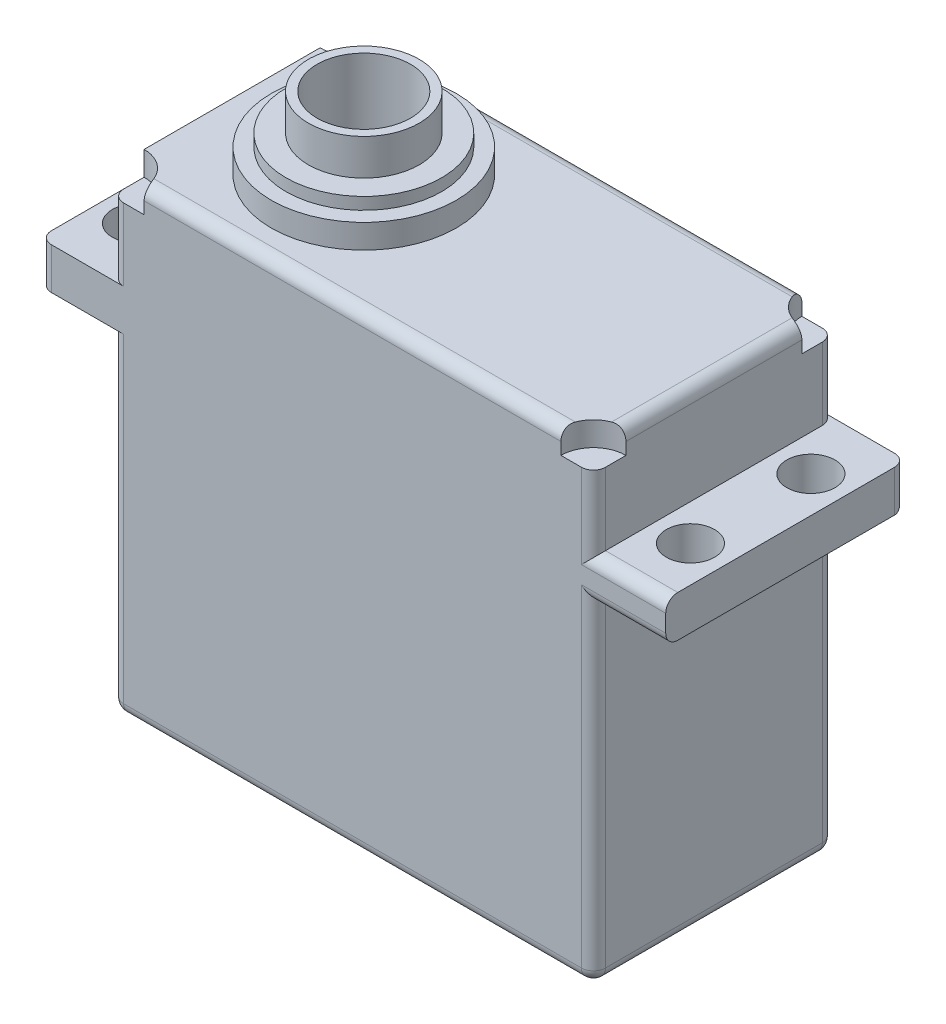
SolidWorks part; units mm, degrees
ref_plane "前视基准面" through (0, 0, 0) normal (0, 0, 1) x (1, 0, 0)
ref_plane "上视基准面" through (0, 0, 0) normal (0, 1, 0) x (1, 0, 0)
ref_plane "右视基准面" through (0, 0, 0) normal (1, 0, 0) x (0, 0, -1)
sketch "草图1" plane through (0, 0, 0) normal (0, 0, 1) x (1, 0, 0)
  line L0 (-157.3317, 38.8231) -> (-117.3317, 38.8231) construction
  line L1 (-157.3317, 38.8231) -> (-157.3317, -0.1769) construction
  line L2 (-157.3317, -0.1769) -> (-117.3317, -0.1769) construction
  line L3 (-117.3317, -0.1769) -> (-117.3317, 38.8231) construction
  line L5 (-157.3317, 38.8231) -> (-117.3317, 38.8231)
  line L6 (-157.3317, 38.8231) -> (-157.3317, -0.1769)
  line L7 (-157.3317, -0.1769) -> (-117.3317, -0.1769)
  line L8 (-117.3317, 38.8231) -> (-117.3317, -0.1769)
extrude "凸台-拉伸2" add sketch "草图1" along normal blind 20
sketch "草图4" plane through (-157.3317, 0, 0) normal (-1, 0, 0) x (0, 0, 1)
  line L0 (0, -0.1769) -> (0, 30.8231) construction
  line L1 (0, 38.8231) -> (0, -0.1769) construction
  line L2 (0, 30.8231) -> (0, 31.8231) construction
  line L3 (0, 31.8231) -> (0, 31.3517) construction
sketch "草图7" plane through (-157.3317, 0, 0) normal (-1, 0, 0) x (0, 0, 1)
  line L0 (20, 38.8231) -> (20, -0.1769) construction
  line L1 (0, 30.8231) -> (20, 30.8231)
  line L2 (0, 30.8231) -> (0, 27.3823)
  line L3 (0, 27.3823) -> (20, 27.3823)
  line L4 (20, 30.8231) -> (20, 27.3823)
extrude "凸台-拉伸3" add sketch "草图7" along normal blind 6
sketch "草图8" plane through (-117.3317, 0, 0) normal (1, 0, 0) x (0, 0, -1)
  line L0 (-20, 5) -> (-20, 30.8231) construction
  line L1 (-20, -0.1769) -> (-20, 38.8231) construction
  line L3 (-20, 30.8231) -> (0, 30.8231)
  line L4 (-20, 30.8231) -> (-20, 27.3823)
  line L5 (-20, 27.3823) -> (0, 27.3823)
  line L6 (0, 30.8231) -> (0, 27.3823)
extrude "凸台-拉伸4" add sketch "草图8" along normal blind 6
sketch "草图10" plane through (0, 30.8231, 0) normal (0, 1, 0) x (1, 0, 0)
  line L0 (-160.3317, 0) -> (-160.3317, -20) construction
  line L1 (-163.3317, 0) -> (-157.3317, 0) construction
  line L2 (-163.3317, -20) -> (-157.3317, -20) construction
  line L3 (-160.3317, 0) -> (-160.3317, -5)
  line L4 (-160.3317, -5) -> (-160.3317, -14.9369)
  circle A0 centre (-160.3317, -5) radius 2
  circle A1 centre (-160.3317, -14.9369) radius 2
  dimension "D1" = 9.9369
extrude "切除-拉伸2" cut sketch "草图10" against normal through all contours L4 A0 L3 | L3 A0 L4 | L4 L0 A1 | L0 L4 A1 region at (-159.4829, 30.8231, 5) region at (-159.4829, 30.8231, 14.9369) region at (-161.1805, 30.8231, 14.9369) region at (-161.1805, 30.8231, 5)
sketch "草图11" plane through (0, 30.8231, 0) normal (0, 1, 0) x (1, 0, 0)
  line L0 (-114.3317, 0) -> (-114.3317, -4.9488) construction
  line L1 (-111.3317, 0) -> (-117.3317, 0) construction
  line L2 (-114.3317, -4.9488) -> (-114.3317, -14.9488) construction
  circle A0 centre (-114.3317, -4.9488) radius 2
  circle A1 centre (-114.3317, -14.9488) radius 2
extrude "切除-拉伸3" cut sketch "草图11" against normal through all
sketch "草图12" plane through (0, 38.8231, 0) normal (0, 1, 0) x (1, 0, 0)
  line L0 (-157.3317, 0) -> (-157.3317, -5) construction
  line L1 (-157.3317, -20) -> (-157.3317, 0) construction
  line L2 (-157.3317, -5) -> (-157.3317, -10) construction
  line L3 (-157.3317, -20) -> (-157.3317, 0) construction
  line L4 (-157.3317, -10) -> (-146.3946, -10) construction
  circle A0 centre (-146.3946, -10) radius 7.6796
extrude "凸台-拉伸5" add sketch "草图12" along normal blind 2
sketch "草图13" plane through (0, 40.8231, 0) normal (0, 1, 0) x (1, 0, 0)
  line L0 (-157.3317, 0) -> (-157.3317, -20) construction
  line L1 (-157.3317, -20) -> (-157.3317, 0) construction
  line L2 (-157.3317, -20) -> (-157.3317, 0) construction
  line L3 (-157.3317, -10) -> (-138.7151, -10) construction
  line L4 (-138.7151, -10) -> (-146.3946, -10) construction
  circle A0 centre (-146.3946, -10) radius 7.6796 construction
  circle A1 centre (-146.3946, -10) radius 6.4555
extrude "凸台-拉伸6" add sketch "草图13" along normal blind 1
sketch "草图14" plane through (0, 41.8231, 0) normal (0, 1, 0) x (1, 0, 0)
  line L0 (-146.3946, -3.5445) -> (-146.3946, -16.4555) construction
  circle A0 centre (-146.3946, -10) radius 6.4555 construction
  circle A1 centre (-146.3946, -10) radius 6.4555 construction
  circle A2 centre (-146.3946, -10) radius 4.5973
extrude "凸台-拉伸7" add sketch "草图14" along normal blind 3
sketch "草图15" plane through (0, 44.8231, 0) normal (0, 1, 0) x (1, 0, 0)
  line L0 (-146.3946, -5.4027) -> (-146.3946, -14.5973) construction
  circle A0 centre (-146.3946, -10) radius 4.5973 construction
  circle A1 centre (-146.3946, -10) radius 3.8797
extrude "切除-拉伸4" cut sketch "草图15" against normal blind 6
sketch "草图17" plane through (0, 38.8231, 0) normal (0, 1, 0) x (1, 0, 0)
  circle A0 centre (-157.3317, -20) radius 2.7
extrude "切除-拉伸9" cut sketch "草图17" against normal blind 2
sketch "草图22" plane through (0, 38.8231, 0) normal (0, 1, 0) x (1, 0, 0)
  circle A0 centre (-117.3317, -20) radius 2.7
extrude "切除-拉伸10" cut sketch "草图22" against normal blind 2
sketch "草图23" plane through (0, 38.8231, 0) normal (0, 1, 0) x (1, 0, 0)
  circle A0 centre (-117.3317, 0) radius 2.7
extrude "切除-拉伸11" cut sketch "草图23" against normal blind 2
sketch "草图24" plane through (0, 38.8231, 0) normal (0, 1, 0) x (1, 0, 0)
  line L0 (-120.0317, 0) -> (-157.3317, 0) construction
  line L1 (-157.3317, -20) -> (-157.3317, 0) construction
  circle A0 centre (-157.3317, 0) radius 2.7
extrude "切除-拉伸12" cut sketch "草图24" against normal blind 2
fillet "圆角1" radius 1 21 edges at (-157.3317, -0.1769, 10) (-117.3317, -0.1769, 10) (-117.3317, 13.6027, 20) (-117.3317, 33.8231, 20) (-114.3317, 27.3823, 20) (-114.3317, 27.3823, 0) (-137.3317, -0.1769, 20) (-114.3317, 30.8231, 20) (-117.3317, 38.8231, 10) (-137.3317, 38.8231, 20) (-157.3317, 33.8231, 0) (-157.3317, 33.8231, 20) (-157.3317, 13.6027, 20) (-163.3317, 29.1027, 20) (-163.3317, 29.1027, 0) (-157.3317, 13.6027, 0) (-137.3317, -0.1769, 0) (-111.3317, 29.1027, 0) (-117.3317, 33.8231, 0) (-117.3317, 13.6027, 0) (-137.3317, 38.8231, 0)
